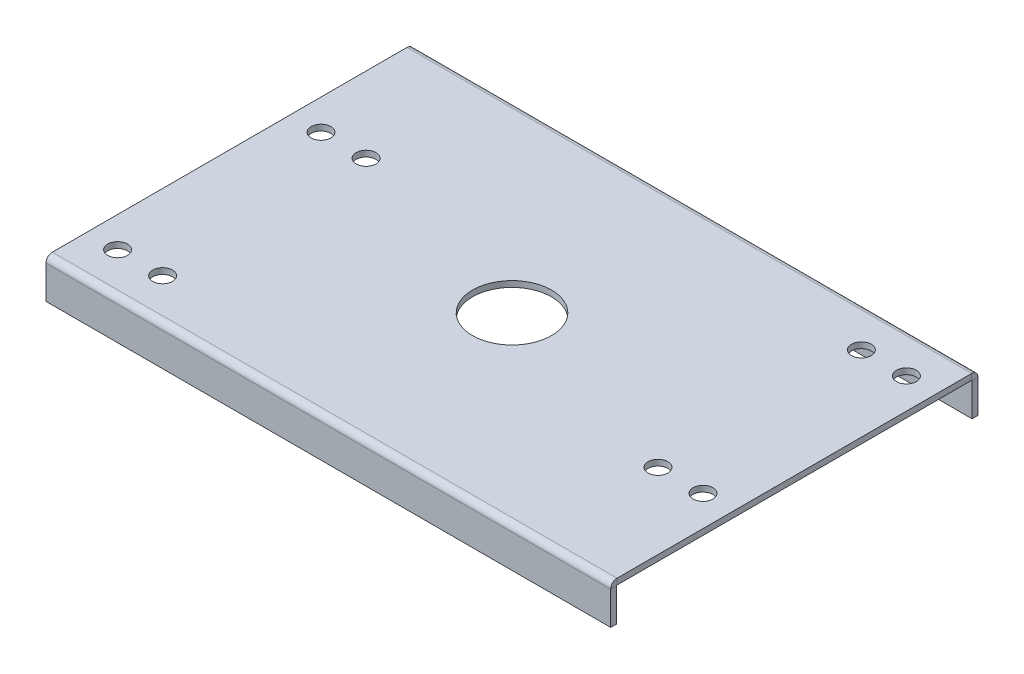
SolidWorks part; units mm, degrees
note: The reader was unsure of these and kept them because the rebuilt part matched: thickness of "Base-Flange1", "Edge-Flange1", "Sheet-Metal2", "Sheet-Metal3", "Sheet-Metal4", "Sheet-Metal5"; flange length of "Edge-Flange1".
ref_plane "Front Plane" through (0, 0, 0) normal (0, 0, 1) x (1, 0, 0)
ref_plane "Top Plane" through (0, 0, 0) normal (0, 1, 0) x (1, 0, 0)
ref_plane "Right Plane" through (0, 0, 0) normal (1, 0, 0) x (0, 0, -1)
sketch "Sketch2" plane through (0, 0, 0) normal (0, 1, 0) x (1, 0, 0)
  line L1 (-71.5, -46.5) -> (71.5, -46.5)
  line L2 (-71.5, -46.5) -> (-71.5, 46.5)
  line L3 (-71.5, 46.5) -> (71.5, 46.5)
  line L4 (71.5, -46.5) -> (71.5, 46.5)
  line L5 (-71.5, -46.5) -> (71.5, 46.5) construction
  line L6 (-71.5, 46.5) -> (71.5, -46.5) construction
  point P0 (0, 0)
  dimension "D1" = 93
  dimension "D2" = 143
base flange "Base-Flange1" sketch "Sketch2" thickness 1.5 reverse thickness direction no parameters "D1"=0.1
edge flange "Edge-Flange1" sketch "Sketch11" flange profiles "Sketch11", "Sketch12" flange angle 90 flange length 10 flange position material inside bend radius 0.1 thickness 1.5 relief rectangular parameters "D6"=10, "D8"=1
sketch "Sketch11" plane through (0, -1.5, 46.5) normal (0, 0, 1) x (-1, 0, 0)
  line L2 (-71.5, 0) -> (-71.5, 8.5)
  line L3 (-71.5, 8.5) -> (71.5, 8.5)
  line L4 (71.5, 8.5) -> (71.5, 0)
  line L7 (71.5, 0) -> (-71.5, 0) construction
  line L8 (71.5, 0) -> (-71.5, 0)
sketch "Sketch12" plane through (0, -1.5, -46.5) normal (0, 0, -1) x (1, 0, 0)
  line L0 (71.5, 0) -> (-71.5, 0) construction
  line L1 (71.5, 0) -> (-71.5, 0)
  line L2 (-71.5, 0) -> (-71.5, 8.5)
  line L3 (-71.5, 8.5) -> (71.5, 8.5)
  line L4 (71.5, 8.5) -> (71.5, 0)
bend "EdgeBend1" bend radius 0.1 bend angle 90 parameters "D5"=1
bend "EdgeBend2" bend radius 0.1 bend angle 90 parameters "D5"=2
sketch "Sketch13" plane through (0, 0, 0) normal (0, 1, 0) x (1, 0, 0)
  circle A0 centre (0, 0) radius 10
extrude "Cut-Extrude1" cut sketch "Sketch13" against normal blind 1.5 normal cut yes
sketch "Sketch14" plane through (0, 0, 0) normal (0, 1, 0) x (1, 0, 0)
  line L1 (71.5, -46.5) -> (71.5, 46.5) construction
  line L3 (-71.5, -46.5) -> (-71.5, 46.5) construction
  line L4 (-71.5, -44.9) -> (71.5, -44.9) construction
  line L5 (71.5, 44.9) -> (-71.5, 44.9) construction
  circle A0 centre (63.775, 36.1) radius 2.5
  circle A1 centre (52.365, 36.1) radius 2.5
  circle A2 centre (52.365, -15.41) radius 2.5
  circle A3 centre (63.775, -15.41) radius 2.5
  circle A4 centre (-63.775, -36.1) radius 2.5
  circle A5 centre (-52.365, -36.1) radius 2.5
  circle A6 centre (-52.365, 15.41) radius 2.5
  circle A7 centre (-63.775, 15.41) radius 2.5
  dimension "D1" = 8.8
  dimension "D3" = 11.41
  dimension "D5" = 8.8
  dimension "D7" = 11.41
  dimension "D2" = 7.725
  dimension "D6" = 7.725
  dimension "D9" = 8.8
  dimension "D10" = 51.51
  dimension "D11" = 51.51
  dimension "D12" = 8.8
  dimension "D4" = 2
  dimension "D8" = 2
extrude "Cut-Extrude2" cut sketch "Sketch14" against normal blind 1.5 normal cut yes
sketch "Bend-Lines1" [suppressed] plane through (0, 0, 0) normal (0, 1, 0) x (1, 0, 0)
sketch "Bounding-Box1" [suppressed] plane through (0, 0, 0) normal (0, 1, 0) x (1, 0, 0)
sheet metal parameters "Sheet-Metal2" thickness 1.5 parameters "D1"=0.1
flat pattern "Flat-Pattern2" [suppressed]
sketch "Bend-Lines2" plane through (0, 0, 0) normal (0, 1, 0) x (1, 0, 0)
sketch3d "Bounding-Box2" [suppressed]
  line L0 (-71.5, 51.5, 0) -> (71.5, 51.5, 0) construction
  line L1 (-71.5, -51.5, 0) -> (71.5, -51.5, 0) construction
  line L2 (-71.5, 51.5, 0) -> (-71.5, -51.5, 0) construction
  line L3 (71.5, 51.5, 0) -> (71.5, -51.5, 0) construction
sheet metal parameters "Sheet-Metal3" thickness 1.5 parameters "D1"=0.1
flat pattern "Flat-Pattern2"
sketch "Bend-Lines2" plane through (0, 0, 0) normal (0, 1, 0) x (1, 0, 0)
  line L0 (71.5, 45.5676) -> (-71.5, 45.5676) construction
  line L1 (-71.5, -45.5676) -> (71.5, -45.5676) construction
  line L2 (71.5, 45.5676) -> (-71.5, 45.5676) construction
  line L3 (-71.5, -45.5676) -> (71.5, -45.5676) construction
sketch3d "Bounding-Box2" [suppressed]
  line L0 (71.5, 54.6352, 0) -> (-71.5, 54.6352, 0) construction
  line L1 (71.5, -54.6352, 0) -> (-71.5, -54.6352, 0) construction
  line L2 (71.5, 54.6352, 0) -> (71.5, -54.6352, 0) construction
  line L3 (-71.5, 54.6352, 0) -> (-71.5, -54.6352, 0) construction
bend of the flat pattern "Flatten-<EdgeBend1>1"
bend of the flat pattern "Flatten-<EdgeBend2>1"
sheet metal parameters "Sheet-Metal4" thickness 1.5 parameters "D1"=0.1
flat pattern "Flat-Pattern2"
sketch "Bend-Lines2" plane through (0, 0, 0) normal (0, 1, 0) x (1, 0, 0)
  line L0 (71.5, 45.5676) -> (-71.5, 45.5676) construction
  line L1 (-71.5, -45.5676) -> (71.5, -45.5676) construction
  line L2 (71.5, 45.5676) -> (-71.5, 45.5676) construction
  line L3 (-71.5, -45.5676) -> (71.5, -45.5676) construction
sketch3d "Bounding-Box2" [suppressed]
  line L0 (71.5, 54.6352, 0) -> (-71.5, 54.6352, 0) construction
  line L1 (71.5, -54.6352, 0) -> (-71.5, -54.6352, 0) construction
  line L2 (71.5, 54.6352, 0) -> (71.5, -54.6352, 0) construction
  line L3 (-71.5, 54.6352, 0) -> (-71.5, -54.6352, 0) construction
bend of the flat pattern "Flatten-<EdgeBend1>1"
bend of the flat pattern "Flatten-<EdgeBend2>1"
sheet metal parameters "Sheet-Metal5" thickness 1.5 parameters "D1"=0.1
flat pattern "Flat-Pattern2"
sketch "Bend-Lines2" plane through (0, 0, 0) normal (0, 1, 0) x (1, 0, 0)
  line L0 (71.5, 45.5676) -> (-71.5, 45.5676) construction
  line L1 (-71.5, -45.5676) -> (71.5, -45.5676) construction
  line L2 (71.5, 45.5676) -> (-71.5, 45.5676) construction
  line L3 (-71.5, -45.5676) -> (71.5, -45.5676) construction
sketch3d "Bounding-Box2" [suppressed]
  line L0 (71.5, 54.6352, 0) -> (-71.5, 54.6352, 0) construction
  line L1 (71.5, -54.6352, 0) -> (-71.5, -54.6352, 0) construction
  line L2 (71.5, 54.6352, 0) -> (71.5, -54.6352, 0) construction
  line L3 (-71.5, 54.6352, 0) -> (-71.5, -54.6352, 0) construction
bend of the flat pattern "Flatten-<EdgeBend1>1"
bend of the flat pattern "Flatten-<EdgeBend2>1"
